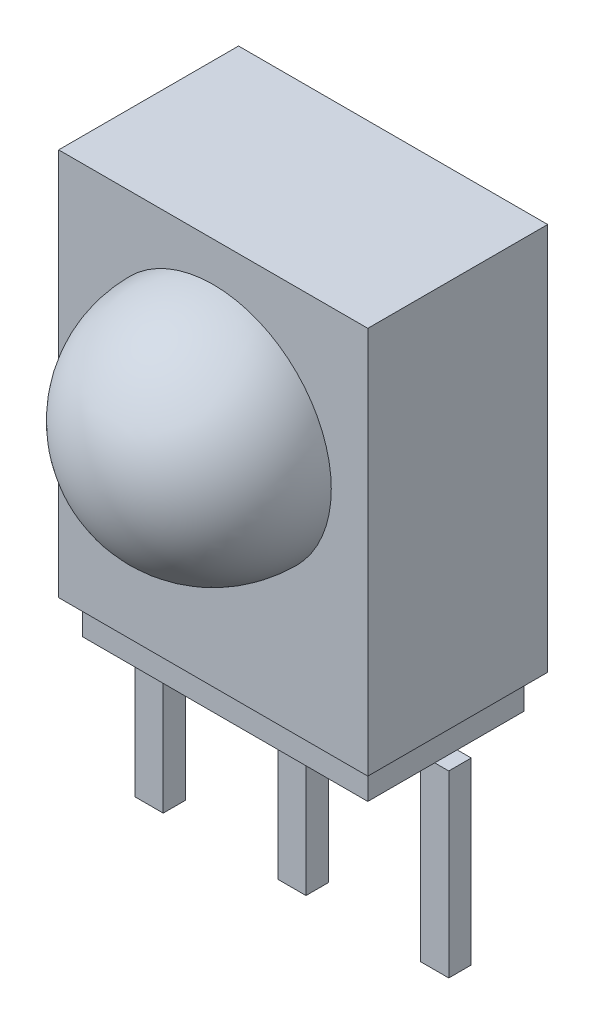
SolidWorks part; units mm, degrees
ref_plane "Front Plane" through (0, 0, 0) normal (0, 0, 1) x (1, 0, 0)
ref_plane "Top Plane" through (0, 0, 0) normal (0, 1, 0) x (1, 0, 0)
ref_plane "Right Plane" through (0, 0, 0) normal (1, 0, 0) x (0, 0, -1)
sketch "Sketch1" plane through (0, 0, 0) normal (0, 0, 1) x (1, 0, 0)
  line L1 (0, 0) -> (5.5, 0)
  line L2 (0, 0) -> (0, 6.9)
  line L3 (0, 6.9) -> (5.5, 6.9)
  line L4 (5.5, 0) -> (5.5, 6.9)
  dimension "D1" = 5.5
  dimension "D2" = 6.9
extrude "Boss-Extrude1" add sketch "Sketch1" along normal blind 3.2
sketch "Sketch4" plane through (0, 0, 3.2) normal (0, 0, 1) x (1, 0, 0)
  circle A0 centre (2.75, 4.1) radius 2.1
extrude "Boss-Extrude2" add sketch "Sketch4" along normal blind 2.1
fillet "Fillet1" radius 2.1 1 edges at (4.85, 4.1, 5.3)
sketch "Sketch5" plane through (0, 0, 0) normal (0, -1, 0) x (1, 0, 0)
  line L1 (0.21, 2.99) -> (5.29, 2.99)
  line L2 (0.21, 2.99) -> (0.21, 0.21)
  line L3 (0.21, 0.21) -> (5.29, 0.21)
  line L4 (5.29, 2.99) -> (5.29, 0.21)
  dimension "D1" = 5.08
  dimension "D2" = 2.78
extrude "Boss-Extrude3" add sketch "Sketch5" along normal blind 0.6
sketch "Sketch7" plane through (0, -0.6, 0) normal (0, -1, 0) x (1, 0, 0)
  line L0 (0, 3.2) -> (0, 0) construction
  line L1 (3, 1.8) -> (2.5, 1.8)
  line L2 (3, 1.8) -> (3, 1.4)
  line L3 (3, 1.4) -> (2.5, 1.4)
  line L4 (2.5, 1.8) -> (2.5, 1.4)
  line L5 (3, 1.8) -> (2.5, 1.4) construction
  line L6 (3, 1.4) -> (2.5, 1.8) construction
  line L7 (0, 0) -> (5.5, 0) construction
  point P0 (2.75, 1.6)
  dimension "D1" = 0.5
  dimension "D2" = 0.4
  dimension "D3" = 2.75
  dimension "D4" = 1.6
extrude "Boss-Extrude5" add sketch "Sketch7" along normal blind 3.19
pattern_linear "LPattern1" count 2 spacing 2.54 along (-1, 0, 0) count 2 spacing 2.54 along (1, 0, 0) of "Boss-Extrude5"
